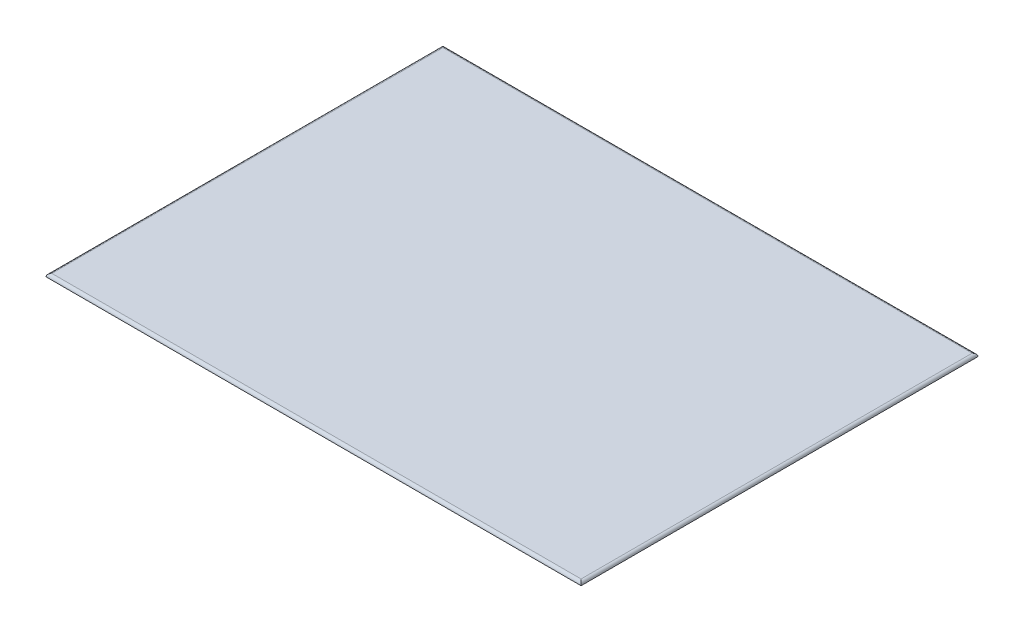
SolidWorks part; units mm, degrees
ref_plane "Front Plane" through (0, 0, 0) normal (0, 0, 1) x (1, 0, 0)
ref_plane "Top Plane" through (0, 0, 0) normal (0, 1, 0) x (1, 0, 0)
ref_plane "Right Plane" through (0, 0, 0) normal (1, 0, 0) x (0, 0, -1)
sketch "Sketch1" plane through (0, 0, 0) normal (0, 1, 0) x (1, 0, 0)
  line L1 (-91, -67.5) -> (91, -67.5)
  line L2 (-91, -67.5) -> (-91, 67.5)
  line L3 (-91, 67.5) -> (91, 67.5)
  line L4 (91, -67.5) -> (91, 67.5)
  line L5 (-91, -67.5) -> (91, 67.5) construction
  line L6 (-91, 67.5) -> (91, -67.5) construction
  point P0 (0, 0)
  dimension "D1" = 182
  dimension "D2" = 135
extrude "Boss-Extrude1" add sketch "Sketch1" along normal blind 9
fillet "Fillet4" radius 1 4 edges at (0, 9, 67.5) (-91, 9, 0) (0, 9, -67.5) (91, 9, 0)
fillet "Fillet5" radius 55 4 edges at (0, 0, -67.5) (-91, 0, 0) (0, 0, 67.5) (91, 0, 0)
